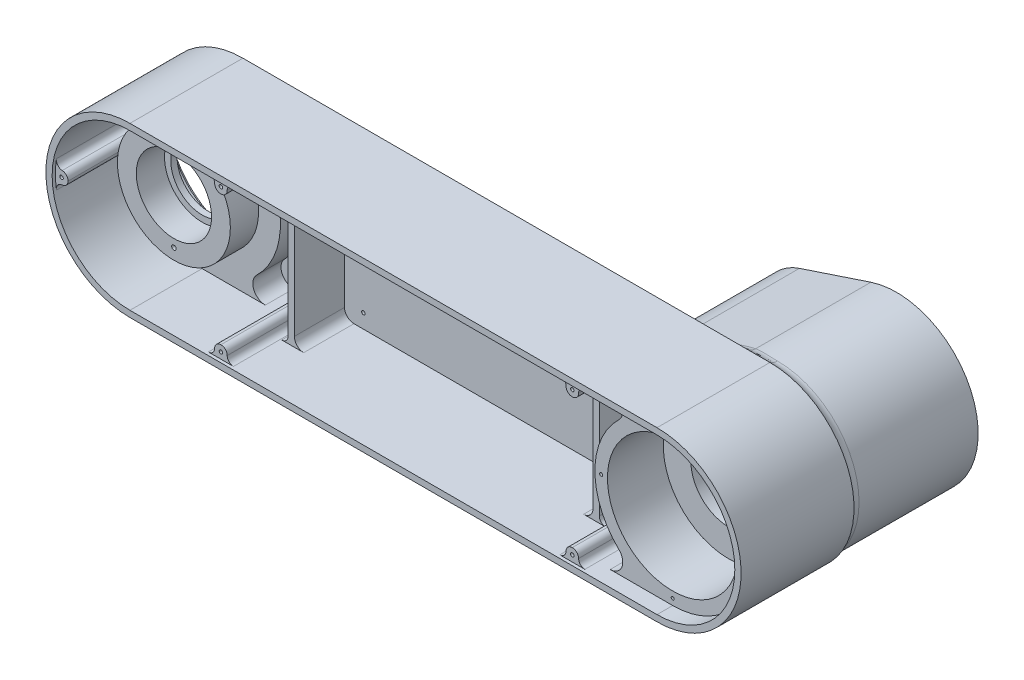
SolidWorks part; units mm, degrees
ref_plane "Front Plane" through (0, 0, 0) normal (0, 0, 1) x (1, 0, 0)
ref_plane "Top Plane" through (0, 0, 0) normal (0, 1, 0) x (1, 0, 0)
ref_plane "Right Plane" through (0, 0, 0) normal (1, 0, 0) x (0, 0, -1)
sketch "Sketch1" plane through (0, 0, 0) normal (0, 0, 1) x (1, 0, 0)
  line L0 (0, 42.545) -> (266.7, 42.545)
  line L1 (0, -42.545) -> (266.7, -42.545)
  line L2 (0, 39.37) -> (266.7, 39.37)
  line L3 (0, -39.37) -> (266.7, -39.37)
  line L4 (266.7, 0) -> (0, 0) construction
  line L5 (133.35, 39.37) -> (133.35, -39.37) construction
  arc A0 (0, 42.545) -> (0, -42.545) centre (0, 0) ccw
  arc A1 (266.7, 42.545) -> (266.7, -42.545) centre (266.7, 0) cw
  arc A2 (266.7, 39.37) -> (266.7, -39.37) centre (266.7, 0) cw
  arc A3 (0, 39.37) -> (0, -39.37) centre (0, 0) ccw
  dimension "D1" = 85.09
  dimension "D2" = 266.7
  dimension "D3" = 3.175
extrude "Boss-Extrude1" add sketch "Sketch1" along normal blind 50.8
extrude "Boss-Extrude2" add sketch "Sketch1<2>" against normal blind 6.35 contours L2 A3 L3 A2 | A1 L0 A0 L1 A3 L2 A2 L3 region at (133.35, 42.1831, 0) region at (133.35, 0, 0)
sketch "Sketch1<2>" plane through (0, 0, 0) normal (0, 0, 1) x (1, 0, 0) same geometry as "Sketch1"
ref_plane "Plane1" through (0, 0, -6.35) normal (0, 0, -1) x (-1, 0, 0)
ref_plane "Plane2" through (0, 0, 0) normal (0, 0, 1) x (1, 0, 0)
sketch "Sketch3" plane through (0, 0, -6.35) normal (0, 0, -1) x (-1, 0, 0)
  circle A0 centre (0, 0) radius 38.1
  dimension "D1" = 76.2
extrude "Cut-Extrude1" cut sketch "Sketch3" against normal blind 5.08
ref_axis "Axis1" through (0, 0, -1.27) along (0, 0, -1)
sketch "Sketch4" plane through (0, 0, 0) normal (0, 0, 1) x (1, 0, 0)
  circle A0 centre (0, 0) radius 31.75
  dimension "D1" = 63.5
extrude "Cut-Extrude2" cut sketch "Sketch4" against normal up to surface (6.35 mm away) contours A0 up to plane "Plane1"
ref_plane "Plane3" through (0, 0, 50.8) normal (0, 0, 1) x (1, 0, 0)
sketch "Sketch15" plane through (0, 0, 0) normal (0, 0, 1) x (1, 0, 0)
  circle A0 centre (0, 0) radius 31.75
  circle A1 centre (0, 0) radius 39.624
  arc A3 (0, 39.37) -> (0, -39.37) centre (0, 0) ccw construction
  dimension "D1" = 63.5
  dimension "D2" = 0.254
extrude "Boss-Extrude6" add sketch "Sketch15" along normal blind 11.0975
sketch "Sketch5" plane through (0, 0, -6.35) normal (0, 0, -1) x (-1, 0, 0)
  line L0 (0, 0) -> (-253.1261, -84.0003) construction
  line L1 (0, 0) -> (-266.7, 0) construction
  line L2 (-253.1261, -84.0003) -> (-266.7, 0) construction
  line L3 (-217.5391, -27.1742) -> (-253.6999, -39.1743)
  line L4 (-253.1261, 84.0003) -> (-266.7, 0) construction
  line L5 (-217.5391, 27.1742) -> (-253.6999, 39.1743)
  line L6 (0, 0) -> (-253.1261, 84.0003) construction
  line L7 (-218.5391, -24.1608) -> (-254.7, -36.1609)
  line L8 (-218.5391, 24.1608) -> (-254.7, 36.1609)
  arc A0 (-254.7, 36.1609) -> (-254.7, -36.1609) centre (-266.7, 0) ccw
  arc A2 (-253.6999, 39.1743) -> (-253.6999, -39.1743) centre (-266.7, 0) ccw
  arc A3 (-217.5391, -27.1742) -> (-217.5391, 27.1742) centre (-226.5569, 0) ccw
  arc A4 (-218.5391, -24.1608) -> (-218.5391, 24.1608) centre (-226.5569, 0) ccw
  dimension "D1" = 266.7
  dimension "D2" = 82.55
  dimension "D3" = 266.7
  dimension "D4" = 85.09
  dimension "D5" = 38.1
  dimension "D6" = 3.175
extrude "Boss-Extrude3" add sketch "Sketch5" along normal up to surface (64.07 mm away)
extrude "Boss-Extrude4" add sketch "Sketch5<2>" along normal up to surface (13.27 mm away) contours L7 A4 L8 A0 region at (255.7198, 0, -6.35)
sketch "Sketch5<2>" plane through (0, 0, -6.35) normal (0, 0, -1) x (-1, 0, 0) same geometry as "Sketch5"
ref_plane "Plane4" through (0, 0, -19.62) normal (0, 0, -1) x (-1, 0, 0)
ref_axis "Axis5" through (266.7, 0, 50.8) along (0, 0, -1)
sketch "Sketch20" plane through (0, 0, 0) normal (0, 0, 1) x (1, 0, 0)
  circle A0 centre (266.7, 0) radius 33.02
  circle A1 centre (266.7, 0) radius 39.37
  arc A2 (266.7, -39.37) -> (266.7, 39.37) centre (266.7, 0) ccw construction
  dimension "D1" = 6.35
extrude "Boss-Extrude9" add sketch "Sketch20" along normal blind 42.8625
extrude "Boss-Extrude10" add sketch "Sketch20<2>" along normal blind 14.59 contours A0 region at (266.7, 0, 0)
sketch "Sketch20<2>" plane through (0, 0, 0) normal (0, 0, 1) x (1, 0, 0) same geometry as "Sketch20"
sketch "Sketch23" plane through (0, 0, -19.62) normal (0, 0, -1) x (-1, 0, 0)
  circle A0 centre (-266.7, 0) radius 19.05
  dimension "D1" = 38.1
extrude "Cut-Extrude6" cut sketch "Sketch23" against normal blind 28.575 from offset 6.35 offset against normal yes
sketch "Sketch24" plane through (0, 0, -19.62) normal (0, 0, -1) x (-1, 0, 0)
  circle A0 centre (-266.7, 0) radius 21.9075
  dimension "D1" = 43.815
extrude "Cut-Extrude7" [suppressed] cut sketch "Sketch24" against normal blind 1.7272 from offset 28.575 offset against normal yes
sketch "Sketch8" plane through (0, 0, 0) normal (0, 0, 1) x (1, 0, 0)
  circle A0 centre (266.7, 0) radius 14.2875
  arc A1 (266.7, -39.37) -> (266.7, 39.37) centre (266.7, 0) ccw construction
  dimension "D1" = 28.575
extrude "Cut-Extrude3" cut sketch "Sketch8" against normal up to surface (19.62 mm away) up to plane "Plane4"
ref_axis "Axis2" through (266.7, 0, -19.62) along (0, 0, 1)
ref_axis "Axis3" through (266.7, 0, 0) along (-1, 0, 0)
ref_axis "Axis4" through (133.35, 39.37, 0) along (0, -1, 0)
sketch "Sketch9" plane through (0, 0, 0) normal (0, 0, 1) x (1, 0, 0)
  line L0 (64.135, 39.37) -> (202.565, 39.37)
  line L1 (202.565, 39.37) -> (202.565, 25.4)
  line L2 (202.565, 25.4) -> (64.135, 25.4)
  line L3 (64.135, 25.4) -> (64.135, 39.37)
  line L4 (64.135, -25.4) -> (64.135, -39.37)
  line L5 (64.135, -39.37) -> (202.565, -39.37)
  line L6 (202.565, -39.37) -> (202.565, -25.4)
  line L7 (202.565, -25.4) -> (64.135, -25.4)
  line L8 (64.135, 25.4) -> (64.135, 0) construction
  line L9 (202.565, 25.4) -> (202.565, -25.4) construction
  line L10 (64.135, 0) -> (64.135, -25.4) construction
  line L11 (266.7, 0) -> (0, 0) construction
  line L12 (133.35, 12.7) -> (133.35, -12.7) construction
  line L13 (133.35, 39.37) -> (133.35, -39.37) construction
  line L14 (64.135, 0) -> (0, 0) construction
  line L15 (202.565, 0) -> (266.7, 0) construction
  point P11 (199.39, 32.1818)
  point P16 (133.35, 0)
  point P20 (67.31, 32.1818)
  point P21 (67.31, -32.1818)
  point P22 (199.39, -32.1818)
  dimension "D1" = 78.74
  dimension "D2" = 25.4
  dimension "D3" = 3.175
  dimension "D4" = 138.43
  dimension "D5" = 25.4
  dimension "D6" = 32.1818
  dimension "D7" = 3.175
sketch "Sketch17" plane through (0, 0, 11.0975) normal (0, 0, 1) x (1, 0, 0)
  circle A0 centre (0, 0) radius 15.875
  circle A1 centre (0, 0) radius 39.624
  circle A2 centre (0, 0) radius 39.624 construction
  dimension "D1" = 31.75
extrude "Boss-Extrude7" add sketch "Sketch17" along normal blind 3.175
sketch "Sketch18" plane through (0, 0, 14.2725) normal (0, 0, 1) x (1, 0, 0)
  circle A0 centre (0, 0) radius 19.05
  circle A1 centre (0, 0) radius 28.575
  dimension "D1" = 38.1
  dimension "D2" = 57.15
extrude "Boss-Extrude8" add sketch "Sketch18" along normal blind 14.2875
ref_plane "Plane7" through (0, 0, 14.2725) normal (0, 0, 1) x (1, 0, 0)
sketch "Sketch19" plane through (0, 0, 14.2725) normal (0, 0, 1) x (1, 0, 0)
  circle A0 centre (0, 0) radius 20.6375
  circle A1 centre (0, 0) radius 21.59
  dimension "D1" = 41.275
  dimension "D2" = 43.18
extrude "Cut-Extrude5" cut sketch "Sketch19" along normal blind 1.7272 from offset 11.1125
fillet "Fillet2" radius 6.35 2 edges at (4.4793, 39.37, 7.1363) (4.4793, -39.37, 7.1363)
sketch "Sketch25" plane through (0, 0, 42.8625) normal (0, 0, 1) x (1, 0, 0)
  line L0 (230.505, 0) -> (266.7, 0) construction
  circle A0 centre (230.505, 0) radius 0.7811
  circle A1 centre (266.7, 36.195) radius 0.781
  circle A2 centre (302.895, 0) radius 0.781
  circle A3 centre (266.7, -36.195) radius 0.781
  point P13 (266.7, 0)
  dimension "D1" = 1.5621
  dimension "D2" = 36.195
  dimension "D3" = 4
extrude "Cut-Extrude8" cut sketch "Sketch25" against normal blind 12.7
sketch "Sketch27" plane through (0, 0, 28.56) normal (0, 0, 1) x (1, 0, 0)
  circle A0 centre (0, 0) radius 23.0124 construction
  point P3 (0, 23.0124)
  point P4 (0, -23.0124)
  dimension "D1" = 46.0248
hole_wizard "#4-40 Tapped Hole1" positions "Sketch29" profile "Sketch28" tap size "#4-40" standard "ANSI Inch"
sketch "Sketch29" plane through (0, 0, 28.56) normal (0, 0, 1) x (1, 0, 0)
  point P0 (0, 23.0124)
  point P3 (0, -23.0124)
sketch "Sketch28" plane through (0, 23.0124, 28.56) normal (1, 0, 0) x (0, -1, 0)
  line L0 (0, 0) -> (0, 8.9342)
  line L1 (0, 8.9342) -> (1.1303, 8.255)
  line L2 (1.1303, 8.255) -> (1.1303, 0)
  line L5 (1.1303, 0) -> (0, 0)
  line L10 (0, 8.9342) -> (-1.1303, 8.255) construction
  line L11 (0, -6.35) -> (0, 107.95) construction
  dimension "Tap Drill Dia." = 2.2606
  dimension "Tap Drill Depth" = 8.255
  dimension "Drill Angle" = 118
cosmetic thread "Hole Thread16" parameters "D1"=6.35, "D2"=2.8448
cosmetic thread "Hole Thread17" parameters "D1"=6.35, "D2"=2.8448
sketch "Sketch30" plane through (0, 0, -19.62) normal (0, 0, -1) x (-1, 0, 0)
  circle A0 centre (-266.7, 0) radius 23.0124 construction
  point P2 (-266.7, -23.0124)
  point P4 (-266.7, 23.0124)
  dimension "D1" = 46.0248
hole_wizard "#4-40 Tapped Hole2" positions "Sketch32" profile "Sketch31" tap size "#4-40" standard "ANSI Inch"
sketch "Sketch32" plane through (0, 0, -19.62) normal (0, 0, -1) x (-1, 0, 0)
  point P0 (-266.7, -23.0124)
  point P3 (-266.7, 23.0124)
sketch "Sketch31" plane through (266.7, -23.0124, -19.62) normal (1, 0, 0) x (0, 1, 0)
  line L0 (0, 0) -> (0, 8.9342)
  line L1 (0, 8.9342) -> (1.1303, 8.255)
  line L2 (1.1303, 8.255) -> (1.1303, 0)
  line L5 (1.1303, 0) -> (0, 0)
  line L10 (0, 8.9342) -> (-1.1303, 8.255) construction
  line L11 (0, -6.35) -> (0, 107.95) construction
  dimension "Tap Drill Dia." = 2.2606
  dimension "Tap Drill Depth" = 8.255
  dimension "Drill Angle" = 118
cosmetic thread "Hole Thread18" parameters "D1"=6.35, "D2"=2.8448
cosmetic thread "Hole Thread19" parameters "D1"=6.35, "D2"=2.8448
fillet "Fillet3" radius 6.35 2 edges at (266.7, 39.37, 21.4312) (266.7, -39.37, 21.4312)
sketch "Sketch33" plane through (0, 0, 0) normal (0, 0, 1) x (1, 0, 0)
  line L0 (47.625, -39.37) -> (47.625, -33.02)
  line L1 (31.9889, -39.37) -> (235.0773, -39.37) construction
  line L2 (47.625, -33.02) -> (41.275, -33.02)
  line L3 (41.275, -33.02) -> (41.275, -39.37)
  line L4 (41.275, -39.37) -> (47.625, -39.37)
  line L5 (44.45, -39.37) -> (44.45, -33.02) construction
  line L6 (225.425, -39.37) -> (225.425, -33.02)
  line L7 (31.9889, -39.37) -> (235.0773, -39.37) construction
  line L8 (225.425, -33.02) -> (219.075, -33.02)
  line L9 (219.075, -33.02) -> (219.075, -39.37)
  line L10 (219.075, -39.37) -> (225.425, -39.37)
  line L11 (222.25, -39.37) -> (222.25, -33.02) construction
  line L12 (-39.2418, -3.175) -> (-32.8918, -3.175)
  line L14 (-32.8918, -3.175) -> (-32.8918, 3.175)
  line L15 (-32.8918, 3.175) -> (-39.2418, 3.175)
  line L16 (-32.8918, 0) -> (-39.37, 0) construction
  line L17 (0, 0) -> (266.7, 0) construction
  line L18 (47.625, 39.37) -> (47.625, 33.02)
  line L19 (41.275, 39.37) -> (47.625, 39.37)
  line L20 (41.275, 33.02) -> (41.275, 39.37)
  line L21 (47.625, 33.02) -> (41.275, 33.02)
  line L22 (219.075, 39.37) -> (225.425, 39.37)
  line L23 (219.075, 33.02) -> (219.075, 39.37)
  line L24 (225.425, 33.02) -> (219.075, 33.02)
  line L25 (225.425, 39.37) -> (225.425, 33.02)
  arc A0 (0, 39.37) -> (0, -39.37) centre (0, 0) ccw construction
  arc A1 (-39.2418, 3.175) -> (-39.2418, -3.175) centre (0, 0) ccw
  point P16 (222.25, -36.195)
  point P17 (44.45, -36.195)
  point P29 (44.45, 36.195)
  point P36 (222.25, 36.195)
  point P41 (-36.195, 0)
  dimension "D1" = 6.35
  dimension "D2" = 6.35
  dimension "D3" = 44.45
  dimension "D4" = 44.45
  dimension "D5" = 6.35
  dimension "D6" = 6.35
  dimension "D7" = 6.35
  dimension "D8" = 6.35
  dimension "D9" = 3.175
extrude "Boss-Extrude11" add sketch "Sketch33" along normal offset from surface (49.2125 mm away) 1.5875 up to face at (133.35, 0, 50.8)
fillet "Fillet4" radius 3.175 18 edges at (219.075, 39.37, 24.6062) (225.425, 39.37, 24.6062) (225.425, 33.02, 24.6062) (219.075, 33.02, 24.6062) (41.275, 39.37, 24.6062) (41.275, 33.02, 24.6062) (47.625, 33.02, 24.6062) (47.625, 39.37, 24.6062) (-32.8918, 3.175, 31.7425) (-32.8918, -3.175, 31.7425) (41.275, -39.37, 24.6062) (41.275, -33.02, 24.6062) (47.625, -33.02, 24.6062) (47.625, -39.37, 24.6062) (219.075, -39.37, 24.6062) (219.075, -33.02, 24.6062) (225.425, -33.02, 24.6062) (225.425, -39.37, 24.6062)
fillet "Fillet5" radius 3.175 2 edges at (-39.2418, -3.175, 31.7425) (-39.2418, 3.175, 31.7425)
ref_plane "Plane8" through (0, 0, 49.2125) normal (0, 0, 1) x (1, 0, 0)
hole_wizard "#2-56 Tapped Hole3" positions "Sketch37" profile "Sketch36" tap size "#2-56" standard "ANSI Inch"
sketch "Sketch37" plane through (0, 0, 49.2125) normal (0, 0, 1) x (1, 0, 0)
  point P0 (222.25, -36.195)
  point P3 (44.45, -36.195)
  point P6 (44.45, 36.195)
  point P8 (-36.195, 0)
  point P11 (222.25, 36.195)
sketch "Sketch36" plane through (222.25, -36.195, 49.2125) normal (1, 0, 0) x (0, -1, 0)
  line L0 (0, 0) -> (0, 13.2342)
  line L1 (0, 13.2342) -> (0.889, 12.7)
  line L2 (0.889, 12.7) -> (0.889, 0)
  line L5 (0.889, 0) -> (0, 0)
  line L10 (0, 13.2342) -> (-0.889, 12.7) construction
  line L11 (0, -6.35) -> (0, 107.95) construction
  dimension "Tap Drill Dia." = 1.778
  dimension "Tap Drill Depth" = 12.7
  dimension "Drill Angle" = 118
cosmetic thread "Hole Thread20" parameters "D1"=11.43, "D2"=2.1844
cosmetic thread "Hole Thread21" parameters "D1"=11.43, "D2"=2.1844
cosmetic thread "Hole Thread22" parameters "D1"=11.43, "D2"=2.1844
cosmetic thread "Hole Thread23" parameters "D1"=11.43, "D2"=2.1844
cosmetic thread "Hole Thread24" parameters "D1"=11.43, "D2"=2.1844
sketch "Sketch38" plane through (0, 0, 0) normal (0, 0, 1) x (1, 0, 0)
  line L0 (217.5391, 27.1742) -> (253.6999, 39.1743) construction
  line L1 (253.6999, -39.1743) -> (217.5391, -27.1742) construction
  line L2 (217.5391, 27.1742) -> (253.6999, 39.1743) construction
  line L3 (253.6999, -39.1743) -> (217.5391, -27.1742) construction
  line L4 (226.5569, 0) -> (226.5569, -12.7564)
  line L5 (226.5569, 0) -> (226.5569, 12.7564)
  line L6 (226.5569, 0) -> (213.8004, 0) construction
  arc A0 (217.5391, 27.1742) -> (217.5391, -27.1742) centre (226.5569, 0) ccw construction
  arc A1 (253.6999, -39.1743) -> (253.6999, 39.1743) centre (266.7, 0) ccw construction
  arc A2 (217.5391, 27.1742) -> (217.5391, -27.1742) centre (226.5569, 0) ccw construction
  arc A3 (253.6999, -39.1743) -> (253.6999, 39.1743) centre (266.7, 0) ccw construction
  arc A4 (226.5569, 12.7564) -> (226.5569, -12.7564) centre (226.5569, 0) ccw
  dimension "D1" = 15.875
  dimension "D3" = 180
extrude "Cut-Extrude9" cut sketch "Sketch38" against normal up to surface (19.62 mm away) contours L5 A4 L4 region at (221.1429, 0, 0) up to face at (266.7, -21.8821, -19.62)
fillet "Fillet6" radius 3.175 2 edges at (226.5569, 12.7564, -9.81) (226.5569, -12.7564, -9.81)
fillet "Fillet7" radius 3.175 4 edges at (225.2177, 11.6306, -19.62) (225.2177, -11.6306, -19.62) (226.5569, 0, -19.62) (213.8004, 0, -19.62)
fillet "Fillet8" radius 6.35 4 edges at (307.975, 0, -6.35) (235.6195, 33.1743, -6.35) (197.9254, 0, -6.35) (235.6195, -33.1743, -6.35)
sketch "Sketch39" plane through (0, 0, -1.27) normal (0, 0, -1) x (-1, 0, 0)
  circle A0 centre (0, 0) radius 34.29 construction
  point P3 (0, 34.29)
  point P4 (-34.29, 0)
  point P5 (0, -34.29)
  point P6 (34.29, 0)
  dimension "D1" = 68.58
hole_wizard "#8-32 Tapped Hole1" positions "Sketch41" profile "Sketch40" tap size "#8-32" standard "ANSI Inch"
sketch "Sketch41" plane through (0, 0, -1.27) normal (0, 0, -1) x (-1, 0, 0)
  point P0 (0, 34.29)
  point P3 (-34.29, 0)
  point P6 (0, -34.29)
  point P9 (34.29, 0)
sketch "Sketch40" plane through (0, 34.29, -1.27) normal (1, 0, 0) x (0, 1, 0)
  line L0 (0, 0) -> (0, 13.4043)
  line L1 (0, 13.4043) -> (1.7272, 12.3665)
  line L2 (1.7272, 12.3665) -> (1.7272, 0)
  line L5 (1.7272, 0) -> (0, 0)
  line L10 (0, 13.4043) -> (-1.7272, 12.3665) construction
  line L11 (0, -6.35) -> (0, 107.95) construction
  dimension "Tap Drill Dia." = 3.4544
  dimension "Tap Drill Depth" = 12.3665
  dimension "Drill Angle" = 118
cosmetic thread "Hole Thread25" parameters "D1"=10.16, "D2"=4.1656
cosmetic thread "Hole Thread26" parameters "D1"=10.16, "D2"=4.1656
cosmetic thread "Hole Thread27" parameters "D1"=10.16, "D2"=4.1656
cosmetic thread "Hole Thread28" parameters "D1"=10.16, "D2"=4.1656
sketch "Sketch42" plane through (0, 0, -19.62) normal (0, 0, -1) x (-1, 0, 0)
  line L0 (-201.1004, 3.175) -> (-207.4504, 3.175)
  line L1 (-207.4504, 3.175) -> (-207.4504, -3.175)
  line L2 (-207.4504, -3.175) -> (-201.1004, -3.175)
  line L3 (-201.1004, -3.175) -> (-201.1004, 3.175)
  line L4 (-201.1004, 0) -> (-207.4504, 0) construction
  line L5 (-243.3134, 32.3822) -> (-245.3134, 26.3554)
  line L6 (-218.5391, 24.1608) -> (-254.7, 36.1609) construction
  line L7 (-245.3134, 26.3554) -> (-239.2866, 24.3554)
  line L8 (-239.2866, 24.3554) -> (-237.2866, 30.3822)
  line L9 (-237.2866, 30.3822) -> (-243.3134, 32.3822)
  line L10 (-240.3, 31.3822) -> (-242.3, 25.3554) construction
  line L11 (-240.3, -31.3822) -> (-242.3, -25.3554) construction
  line L12 (-239.2866, -24.3554) -> (-237.2866, -30.3822)
  line L13 (-237.2866, -30.3822) -> (-243.3134, -32.3822)
  line L14 (-243.3134, -32.3822) -> (-245.3134, -26.3554)
  line L15 (-245.3134, -26.3554) -> (-239.2866, -24.3554)
  line L16 (-298.45, 0) -> (-304.8, 0) construction
  line L17 (-304.8, 3.175) -> (-298.45, 3.175)
  line L18 (-304.8, 3.175) -> (-304.8, -3.175)
  line L19 (-304.8, -3.175) -> (-298.45, -3.175)
  line L20 (-298.45, 3.175) -> (-298.45, -3.175)
  arc A0 (-218.5391, -24.1608) -> (-218.5391, 24.1608) centre (-226.5569, 0) ccw construction
  arc A2 (-254.7, 36.1609) -> (-254.7, -36.1609) centre (-266.7, 0) ccw construction
  point P10 (-204.2754, 0)
  point P20 (-241.3, 28.3688)
  point P21 (-241.3, -28.3688)
  point P37 (-301.625, 0)
  dimension "D1" = 6.35
  dimension "D2" = 6.35
  dimension "D3" = 3.175
  dimension "D4" = 6.35
  dimension "D5" = 6.35
  dimension "D6" = 25.4
  dimension "D7" = 6.35
  dimension "D8" = 6.35
  dimension "D9" = 3.175
extrude "Boss-Extrude12" add sketch "Sketch42" along normal offset from surface (49.2125 mm away) 1.5875 up to face at (244.7849, 0, -70.42)
fillet "Fillet9" radius 3.175 12 edges at (237.2866, -30.3822, -44.2262) (239.2866, -24.3554, -44.2262) (245.3134, -26.3554, -44.2262) (243.3134, -32.3822, -44.2262) (298.45, 3.175, -44.2262) (298.45, -3.175, -44.2262) (237.2866, 30.3822, -44.2262) (243.3134, 32.3822, -44.2262) (239.2866, 24.3554, -44.2262) (245.3134, 26.3554, -44.2262) (207.4504, -3.175, -44.2262) (207.4504, 3.175, -44.2262)
fillet "Fillet10" radius 3.175 4 edges at (304.6675, 3.175, -44.2262) (304.6675, -3.175, -44.2262) (201.2992, -3.175, -44.2262) (201.2992, 3.175, -44.2262)
ref_plane "Plane9" through (0, 0, -68.8325) normal (0, 0, -1) x (-1, 0, 0)
hole_wizard "#2-56 Tapped Hole4" positions "Sketch46" profile "Sketch45" tap size "#2-56" standard "ANSI Inch"
sketch "Sketch46" plane through (0, 0, -68.8325) normal (0, 0, -1) x (-1, 0, 0)
  point P0 (-204.2754, 0)
  point P2 (-241.3, 28.3688)
  point P4 (-301.625, 0)
  point P6 (-241.3, -28.3688)
sketch "Sketch45" plane through (204.2754, 0, -68.8325) normal (1, 0, 0) x (0, 1, 0)
  line L0 (0, 0) -> (0, 8.4082)
  line L1 (0, 8.4082) -> (0.889, 7.874)
  line L2 (0.889, 7.874) -> (0.889, 0)
  line L5 (0.889, 0) -> (0, 0)
  line L10 (0, 8.4082) -> (-0.889, 7.874) construction
  line L11 (0, -6.35) -> (0, 107.95) construction
  dimension "Tap Drill Dia." = 1.778
  dimension "Tap Drill Depth" = 7.874
  dimension "Drill Angle" = 118
cosmetic thread "Hole Thread29" parameters "D1"=6.35, "D2"=2.1844
cosmetic thread "Hole Thread30" parameters "D1"=6.35, "D2"=2.1844
cosmetic thread "Hole Thread31" parameters "D1"=6.35, "D2"=2.1844
cosmetic thread "Hole Thread32" parameters "D1"=6.35, "D2"=2.1844
hole_wizard "#2-56 Tapped Hole5" positions "Sketch48" profile "Sketch47" tap size "#2-56" standard "ANSI Inch"
sketch "Sketch48" plane through (0, 0, 0) normal (0, 0, 1) x (1, 0, 0)
  point P0 (199.39, -32.1818)
  point P3 (199.39, 32.1818)
  point P6 (67.31, 32.1818)
  point P9 (67.31, -32.1818)
sketch "Sketch47" plane through (199.39, -32.1818, 0) normal (1, 0, 0) x (0, -1, 0)
  line L0 (0, 0) -> (0, 3.7092)
  line L1 (0, 3.7092) -> (0.889, 3.175)
  line L2 (0.889, 3.175) -> (0.889, 0)
  line L5 (0.889, 0) -> (0, 0)
  line L10 (0, 3.7092) -> (-0.889, 3.175) construction
  line L11 (0, -6.35) -> (0, 107.95) construction
  dimension "Tap Drill Dia." = 1.778
  dimension "Tap Drill Depth" = 3.175
  dimension "Drill Angle" = 118
cosmetic thread "Hole Thread33" parameters "D1"=3.175, "D2"=2.1844
cosmetic thread "Hole Thread34" parameters "D1"=3.175, "D2"=2.1844
cosmetic thread "Hole Thread35" parameters "D1"=3.175, "D2"=2.1844
cosmetic thread "Hole Thread36" parameters "D1"=3.175, "D2"=2.1844
sketch "Sketch49" plane through (0, 0, 0) normal (0, 0, 1) x (1, 0, 0)
  line L0 (215.9, 39.37) -> (50.8, 39.37) construction
  line L1 (54.61, 39.37) -> (57.785, 39.37)
  line L2 (54.61, 39.37) -> (54.61, -39.37)
  line L3 (54.61, -39.37) -> (57.785, -39.37)
  line L4 (57.785, 39.37) -> (57.785, -39.37)
  line L5 (50.8, -39.37) -> (215.9, -39.37) construction
  line L6 (266.7, 39.37) -> (0, 39.37) construction
  line L7 (208.915, 39.37) -> (212.09, 39.37)
  line L8 (208.915, 39.37) -> (208.915, -39.37)
  line L9 (208.915, -39.37) -> (212.09, -39.37)
  line L10 (212.09, 39.37) -> (212.09, -39.37)
  dimension "D1" = 3.175
  dimension "D2" = 9.525
  dimension "D3" = 3.175
  dimension "D4" = 9.525
extrude "Boss-Extrude13" add sketch "Sketch49" along normal blind 25.4
fillet "Fillet11" radius 3.175 4 edges at (225.2177, 11.6306, 0) (226.5569, 0, 0) (225.2177, -11.6306, 0) (213.8004, 0, 0)
fillet "Fillet13" radius 3.175 4 edges at (212.09, 39.37, 12.7) (212.09, -39.37, 12.7) (54.61, -39.37, 12.7) (54.61, 39.37, 12.7)
fillet "Fillet14" radius 4.7625 4 edges at (208.915, 39.37, 12.7) (208.915, -39.37, 12.7) (57.785, -39.37, 12.7) (57.785, 39.37, 12.7)
equation "\"D1@Sketch9\"= \"D1@Sketch1\" - 2 * \"D3@Sketch1\""
equation "\"D1@Boss-Extrude6\"=.61191in - .05in - .125"
equation "\"D1@Boss-Extrude8\"=7/16 + .125 "
